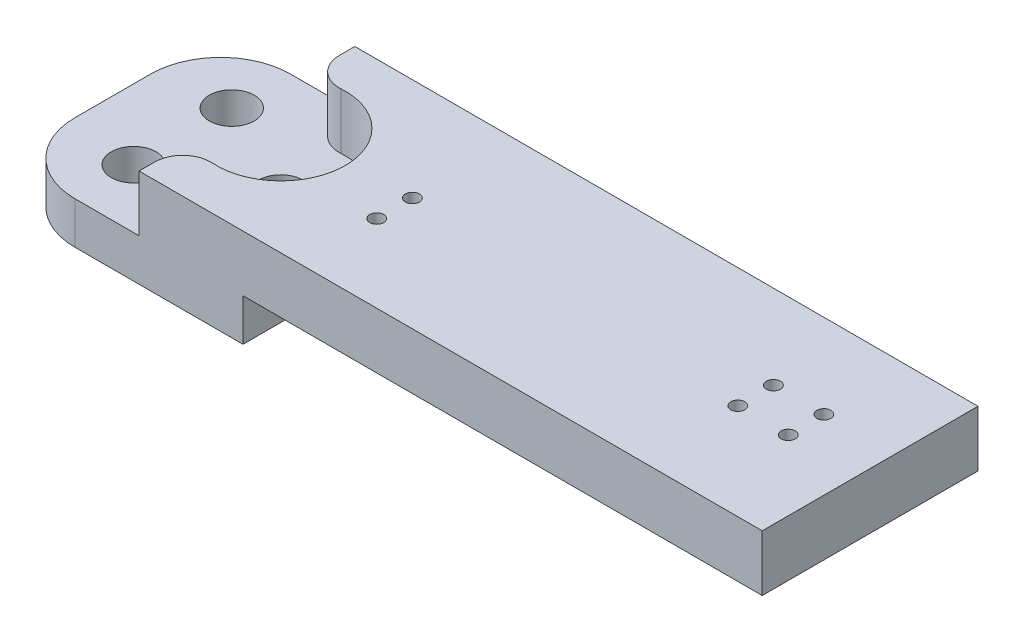
SolidWorks part; units mm, degrees
ref_plane "前视基准面" through (0, 0, 0) normal (0, 0, 1) x (1, 0, 0)
ref_plane "上视基准面" through (0, 0, 0) normal (0, 1, 0) x (1, 0, 0)
ref_plane "右视基准面" through (0, 0, 0) normal (1, 0, 0) x (0, 0, -1)
other "Configuration Table"
sketch "草图1" plane through (0, 0, 0) normal (0, 1, 0) x (1, 0, 0)
  line L0 (93.0116, 72.586) -> (93.0217, 72.586)
  line L1 (93.0116, 72.586) -> (93.0116, 72.6063)
  line L2 (93.0116, 72.586) -> (93.0217, 72.586)
  line L3 (93.0116, 72.586) -> (93.0116, 72.6063)
  line L4 (93.0116, 72.586) -> (93.0217, 72.586)
  line L5 (93.0116, 72.586) -> (93.0116, 72.6063)
  line L6 (103.9336, 94.432) -> (103.9437, 94.432)
  line L7 (103.9336, 94.432) -> (103.9336, 94.4523)
  line L8 (168.0366, 84.272) -> (168.0366, 84.2822)
  line L9 (168.0366, 84.272) -> (168.0163, 84.272)
  line L10 (158.1141, 95.514) -> (158.1039, 95.514)
  line L11 (158.1141, 95.514) -> (158.1141, 95.4938)
  line L12 (107.4956, 78.486) -> (107.4956, 78.4759)
  line L13 (107.4956, 78.486) -> (107.5158, 78.486)
  line L14 (161.3376, 94.432) -> (161.3477, 94.432)
  line L15 (161.3376, 94.432) -> (161.3376, 94.4523)
  line L16 (98.6366, 91.661) -> (98.6366, 91.6712)
  line L17 (98.6366, 91.661) -> (98.6163, 91.661)
  line L18 (100.7956, 90.686) -> (100.7956, 90.6962)
  line L19 (100.7956, 90.686) -> (100.7753, 90.686)
  line L20 (164.6396, 89.352) -> (164.6294, 89.352)
  line L21 (164.6396, 89.352) -> (164.6396, 89.3318)
  line L22 (94.7616, 80.161) -> (94.7514, 80.161)
  line L23 (94.7616, 80.161) -> (94.7616, 80.1408)
  line L24 (168.1956, 81.732) -> (168.1854, 81.732)
  line L25 (168.1956, 81.732) -> (168.1956, 81.7118)
  line L26 (178.2616, 97.586) -> (178.2514, 97.586)
  line L27 (178.2616, 97.586) -> (178.2616, 97.5658)
  line L28 (172.9366, 94.061) -> (172.9366, 94.0712)
  line L29 (172.9366, 94.061) -> (172.9163, 94.061)
  line L30 (113.8866, 87.236) -> (113.8764, 87.236)
  line L31 (113.8866, 87.236) -> (113.8866, 87.2158)
  line L32 (165.6556, 84.272) -> (165.6556, 84.2619)
  line L33 (165.6556, 84.272) -> (165.6758, 84.272)
  line L34 (115.6116, 92.886) -> (115.6116, 92.8759)
  line L35 (115.6116, 92.886) -> (115.6318, 92.886)
  line L36 (99.6366, 91.636) -> (99.6366, 91.6462)
  line L37 (99.6366, 91.636) -> (99.6163, 91.636)
  line L38 (106.2116, 94.486) -> (106.2217, 94.486)
  line L39 (106.2116, 94.486) -> (106.2116, 94.5063)
  line L40 (176.0696, 87.066) -> (176.0696, 87.0762)
  line L41 (176.0696, 87.066) -> (176.0493, 87.066)
  line L42 (175.5866, 82.236) -> (175.5967, 82.236)
  line L43 (175.5866, 82.236) -> (175.5866, 82.2563)
  line L44 (175.5616, 90.368) -> (175.5717, 90.368)
  line L45 (175.5616, 90.368) -> (175.5616, 90.3883)
  line L46 (95.0616, 85.036) -> (95.0514, 85.036)
  line L47 (95.0616, 85.036) -> (95.0616, 85.0158)
  line L48 (170.3616, 84.526) -> (170.3616, 84.5159)
  line L49 (170.3616, 84.526) -> (170.3818, 84.526)
  line L50 (156.2576, 97.48) -> (156.2576, 97.4699)
  line L51 (156.2576, 97.48) -> (156.2778, 97.48)
  line L52 (165.4016, 77.414) -> (165.4016, 77.4039)
  line L53 (165.4016, 77.414) -> (165.4218, 77.414)
  line L54 (166.1636, 90.368) -> (166.1737, 90.368)
  line L55 (166.1636, 90.368) -> (166.1636, 90.3883)
  line L56 (170.4816, 89.098) -> (170.4816, 89.1082)
  line L57 (170.4816, 89.098) -> (170.4613, 89.098)
  line L58 (114.7116, 89.836) -> (114.7116, 89.8462)
  line L59 (114.7116, 89.836) -> (114.6913, 89.836)
  line L60 (174.4366, 96.386) -> (174.4366, 96.3962)
  line L61 (174.4366, 96.386) -> (174.4163, 96.386)
  line L62 (186.9916, 88.59) -> (186.9916, 88.5799)
  line L63 (186.9916, 88.59) -> (187.0118, 88.59)
  line L64 (103.7141, 76.086) -> (103.7242, 76.086)
  line L65 (103.7141, 76.086) -> (103.7141, 76.1063)
  line L66 (184.9436, 88.0845) -> (184.9436, 88.0744)
  line L67 (184.9436, 88.0845) -> (184.9638, 88.0845)
  line L68 (122.8116, 84.011) -> (122.8217, 84.011)
  line L69 (122.8116, 84.011) -> (122.8116, 84.0313)
  line L70 (120.9516, 99.512) -> (120.9414, 99.512)
  line L71 (120.9516, 99.512) -> (120.9516, 99.4918)
  line L72 (173.1116, 80.97) -> (173.1116, 80.9802)
  line L73 (173.1116, 80.97) -> (173.0913, 80.97)
  line L74 (117.6116, 92.911) -> (117.6116, 92.9212)
  line L75 (117.6116, 92.911) -> (117.5913, 92.911)
  line L76 (112.3156, 92.908) -> (112.3257, 92.908)
  line L77 (112.3156, 92.908) -> (112.3156, 92.9283)
  line L78 (120.9516, 97.988) -> (120.9414, 97.988)
  line L79 (120.9516, 97.988) -> (120.9516, 97.9678)
  line L80 (163.1156, 87.32) -> (163.1156, 87.3099)
  line L81 (163.1156, 87.32) -> (163.1358, 87.32)
  line L82 (103.7141, 75.086) -> (103.7039, 75.086)
  line L83 (103.7141, 75.086) -> (103.7141, 75.0658)
  line L84 (116.6366, 92.886) -> (116.6366, 92.8962)
  line L85 (116.6366, 92.886) -> (116.6163, 92.886)
  line L86 (108.2516, 75.636) -> (108.2414, 75.636)
  line L87 (108.2516, 75.636) -> (108.2516, 75.6158)
  line L88 (185.9756, 88.082) -> (185.9756, 88.0922)
  line L89 (185.9756, 88.082) -> (185.9553, 88.082)
  line L90 (104.5616, 81.486) -> (104.5514, 81.486)
  line L91 (104.5616, 81.486) -> (104.5616, 81.4658)
  line L92 (101.8116, 90.686) -> (101.8116, 90.6962)
  line L93 (101.8116, 90.686) -> (101.7913, 90.686)
  line L94 (102.8616, 82.886) -> (102.8616, 82.8759)
  line L95 (102.8616, 82.886) -> (102.8818, 82.886)
  line L96 (106.2116, 95.486) -> (106.2217, 95.486)
  line L97 (106.2116, 95.486) -> (106.2116, 95.5063)
  line L98 (101.1396, 75.636) -> (101.1396, 75.6462)
  line L99 (101.1396, 75.636) -> (101.1193, 75.636)
  line L100 (97.0116, 90.486) -> (97.0014, 90.486)
  line L101 (97.0116, 90.486) -> (97.0116, 90.4658)
  line L102 (102.7866, 90.786) -> (102.7866, 90.7962)
  line L103 (102.7866, 90.786) -> (102.7663, 90.786)
  line L104 (167.7116, 87.911) -> (167.7116, 87.9009)
  line L105 (167.7116, 87.911) -> (167.7318, 87.911)
  line L106 (166.1636, 91.384) -> (166.1534, 91.384)
  line L107 (166.1636, 91.384) -> (166.1636, 91.3638)
  line L108 (97.0116, 89.486) -> (97.0014, 89.486)
  line L109 (97.0116, 89.486) -> (97.0116, 89.4658)
  line L110 (100.1236, 75.636) -> (100.1236, 75.6462)
  line L111 (100.1236, 75.636) -> (100.1033, 75.636)
  line L112 (172.0866, 80.62) -> (172.0866, 80.6302)
  line L113 (172.0866, 80.62) -> (172.0663, 80.62)
  line L114 (108.4991, 87.3235) -> (108.4991, 87.3337)
  line L115 (108.4991, 87.3235) -> (108.4788, 87.3235)
  line L116 (185.2136, 89.86) -> (185.2237, 89.86)
  line L117 (185.2136, 89.86) -> (185.2136, 89.8803)
  line L118 (173.2756, 88.844) -> (173.2756, 88.8339)
  line L119 (173.2756, 88.844) -> (173.2958, 88.844)
  line L120 (171.9366, 94.036) -> (171.9366, 94.0259)
  line L121 (171.9366, 94.036) -> (171.9568, 94.036)
  line L122 (170.2276, 93.924) -> (170.2276, 93.9139)
  line L123 (170.2276, 93.924) -> (170.2478, 93.924)
  line L124 (175.5866, 79.586) -> (175.5967, 79.586)
  line L125 (175.5866, 79.586) -> (175.5866, 79.6063)
  line L126 (180.5391, 83.002) -> (180.5492, 83.002)
  line L127 (180.5391, 83.002) -> (180.5391, 83.0223)
  line L128 (119.2116, 84.011) -> (119.2217, 84.011)
  line L129 (119.2116, 84.011) -> (119.2116, 84.0313)
  line L130 (107.7116, 74.186) -> (107.7217, 74.186)
  line L131 (107.7116, 74.186) -> (107.7116, 74.2063)
  line L132 (107.6116, 80.886) -> (107.6116, 80.8759)
  line L133 (107.6116, 80.886) -> (107.6318, 80.886)
  line L134 (103.7866, 91.561) -> (103.7866, 91.5712)
  line L135 (103.7866, 91.561) -> (103.7663, 91.561)
  line L136 (108.5866, 80.886) -> (108.5866, 80.8759)
  line L137 (108.5866, 80.886) -> (108.6068, 80.886)
  line L138 (165.5262, 99.6668) -> (182.5442, 99.6668)
  line L139 (182.5442, 99.6668) -> (182.5442, 96.8728)
  line L140 (96.8824, 77.3808) -> (96.6276, 77.6237)
  line L141 (96.6276, 77.6237) -> (96.3469, 77.836)
  line L142 (96.0438, 78.0149) -> (95.7224, 78.1582)
  line L143 (95.7224, 78.1582) -> (95.3867, 78.264)
  line L144 (164.7642, 100.4288) -> (165.5262, 99.6668)
  line L145 (164.5669, 88.1518) -> (164.4036, 88.0947)
  line L146 (164.4036, 88.0947) -> (164.2571, 88.0026)
  line L147 (164.2571, 88.0026) -> (164.1348, 87.8803)
  line L148 (164.1348, 87.8803) -> (164.0427, 87.7338)
  line L149 (164.1348, 86.917) -> (164.2571, 86.7947)
  line L150 (164.2571, 86.7947) -> (164.4036, 86.7026)
  line L151 (164.4036, 86.7026) -> (164.5669, 86.6455)
  line L152 (164.5669, 86.6455) -> (164.7388, 86.6261)
  line L153 (164.7388, 86.6261) -> (164.9107, 86.6455)
  line L154 (165.4919, 87.2267) -> (165.5113, 87.3986)
  line L155 (165.5113, 87.3986) -> (165.4919, 87.5705)
  line L156 (165.4919, 87.5705) -> (165.4348, 87.7338)
  line L157 (165.4348, 87.7338) -> (165.3427, 87.8803)
  line L158 (165.3427, 87.8803) -> (165.2204, 88.0026)
  line L159 (137.7132, 95.8568) -> (137.144, 95.8353)
  line L160 (151.1426, 85.7394) -> (151.3379, 85.9384)
  line L161 (151.8102, 87.2208) -> (151.7905, 87.499)
  line L162 (151.7905, 87.499) -> (151.7319, 87.7716)
  line L163 (151.7319, 87.7716) -> (151.6355, 88.0333)
  line L164 (151.6355, 88.0333) -> (151.5033, 88.2788)
  line L165 (151.5033, 88.2788) -> (151.3379, 88.5033)
  line L166 (139.9573, 95.5149) -> (139.4075, 95.6639)
  line L167 (139.4075, 95.6639) -> (138.8482, 95.7709)
  line L168 (138.8482, 95.7709) -> (138.2823, 95.8353)
  line L169 (138.2823, 95.8353) -> (137.7132, 95.8568)
  line L170 (118.0282, 100.4288) -> (164.7642, 100.4288)
  line L171 (182.5442, 96.8728) -> (182.6167, 96.5552)
  line L172 (118.0282, 98.6508) -> (118.0282, 100.4288)
  line L173 (182.6167, 96.5552) -> (182.7281, 96.249)
  line L174 (97.8352, 98.6508) -> (118.0282, 98.6508)
  line L175 (182.7281, 96.249) -> (182.8767, 95.9591)
  line L176 (97.8352, 94.5868) -> (97.8352, 98.6508)
  line L177 (182.8767, 95.9591) -> (183.0603, 95.6899)
  line L178 (97.8236, 94.2665) -> (97.8352, 94.5868)
  line L179 (183.0603, 95.6899) -> (183.2759, 95.4456)
  line L180 (97.7731, 93.95) -> (97.8236, 94.2665)
  line L181 (183.2759, 95.4456) -> (183.5202, 95.23)
  line L182 (97.6844, 93.642) -> (97.7731, 93.95)
  line L183 (183.5202, 95.23) -> (183.7894, 95.0464)
  line L184 (97.5587, 93.3471) -> (97.6844, 93.642)
  line L185 (183.7894, 95.0464) -> (184.0793, 94.8978)
  line L186 (97.398, 93.0697) -> (97.5587, 93.3471)
  line L187 (184.0793, 94.8978) -> (184.3855, 94.7864)
  line L188 (97.2046, 92.8141) -> (97.398, 93.0697)
  line L189 (184.3855, 94.7864) -> (184.7032, 94.7138)
  line L190 (96.9815, 92.5839) -> (97.2046, 92.8141)
  line L191 (184.7032, 94.7138) -> (188.8942, 94.7138)
  line L192 (96.732, 92.3827) -> (96.9815, 92.5839)
  line L193 (188.8942, 94.7138) -> (188.8942, 78.3308)
  line L194 (96.4599, 92.2134) -> (96.732, 92.3827)
  line L195 (188.8942, 78.3308) -> (177.4642, 78.3308)
  line L196 (96.169, 92.0786) -> (96.4599, 92.2134)
  line L197 (177.4642, 78.3308) -> (177.1354, 78.2515)
  line L198 (95.864, 91.9802) -> (96.169, 92.0786)
  line L199 (177.1354, 78.2515) -> (176.8186, 78.1328)
  line L200 (95.5492, 91.9198) -> (95.864, 91.9802)
  line L201 (176.8186, 78.1328) -> (176.5187, 77.9765)
  line L202 (93.0092, 91.9198) -> (95.5492, 91.9198)
  line L203 (176.5187, 77.9765) -> (176.2399, 77.7849)
  line L204 (93.0092, 88.1098) -> (93.0092, 91.9198)
  line L205 (176.2399, 77.7849) -> (175.9866, 77.5609)
  line L206 (95.5492, 88.1098) -> (93.0092, 88.1098)
  line L207 (175.9866, 77.5609) -> (175.7623, 77.3077)
  line L208 (95.7229, 88.0427) -> (95.5492, 88.1098)
  line L209 (175.7623, 77.3077) -> (175.5704, 77.0292)
  line L210 (95.878, 87.9395) -> (95.7229, 88.0427)
  line L211 (175.5704, 77.0292) -> (175.4138, 76.7294)
  line L212 (96.007, 87.8051) -> (95.878, 87.9395)
  line L213 (175.4138, 76.7294) -> (175.2949, 76.4128)
  line L214 (96.1038, 87.6459) -> (96.007, 87.8051)
  line L215 (175.2949, 76.4128) -> (175.2152, 76.084)
  line L216 (96.1638, 87.4695) -> (96.1038, 87.6459)
  line L217 (175.2152, 76.084) -> (175.1761, 75.7481)
  line L218 (96.1842, 87.2843) -> (96.1638, 87.4695)
  line L219 (175.1761, 75.7481) -> (175.1782, 75.4098)
  line L220 (96.1638, 87.0992) -> (96.1842, 87.2843)
  line L221 (175.1782, 75.4098) -> (175.1782, 75.0288)
  line L222 (96.1038, 86.9228) -> (96.1638, 87.0992)
  line L223 (175.1782, 75.0288) -> (161.4622, 75.0288)
  line L224 (96.007, 86.7636) -> (96.1038, 86.9228)
  line L225 (161.4622, 75.0288) -> (161.4622, 72.6158)
  line L226 (95.878, 86.6292) -> (96.007, 86.7636)
  line L227 (161.4622, 72.6158) -> (97.5812, 72.6158)
  line L228 (95.7229, 86.526) -> (95.878, 86.6292)
  line L229 (97.5812, 72.6158) -> (97.5812, 76.1718)
  line L230 (95.5492, 86.4588) -> (95.7229, 86.526)
  line L231 (97.5812, 76.1718) -> (97.4595, 76.5021)
  line L232 (93.0092, 86.4588) -> (95.5492, 86.4588)
  line L233 (97.4595, 76.5021) -> (97.301, 76.8164)
  line L234 (93.0092, 78.3308) -> (93.0092, 86.4588)
  line L235 (97.301, 76.8164) -> (97.1078, 77.1105)
  line L236 (95.0412, 78.3308) -> (93.0092, 78.3308)
  line L237 (97.1078, 77.1105) -> (96.8824, 77.3808)
  line L238 (95.3867, 78.264) -> (95.0412, 78.3308)
  line L239 (138.4395, 78.6481) -> (139.0038, 78.7263)
  line L240 (137.871, 78.6089) -> (138.4395, 78.6481)
  line L241 (137.3013, 78.6089) -> (137.871, 78.6089)
  line L242 (96.3469, 77.836) -> (96.0438, 78.0149)
  line L243 (164.7388, 88.1712) -> (164.5669, 88.1518)
  line L244 (164.9107, 88.1518) -> (164.7388, 88.1712)
  line L245 (165.0739, 88.0947) -> (164.9107, 88.1518)
  line L246 (165.2204, 88.0026) -> (165.0739, 88.0947)
  line L247 (134.0044, 79.4194) -> (134.5262, 79.1906)
  line L248 (133.4996, 79.6836) -> (134.0044, 79.4194)
  line L249 (133.0142, 79.9818) -> (133.4996, 79.6836)
  line L250 (123.9972, 85.6968) -> (133.0142, 79.9818)
  line L251 (123.8108, 85.8961) -> (123.9972, 85.6968)
  line L252 (165.4348, 87.0635) -> (165.4919, 87.2267)
  line L253 (165.3427, 86.917) -> (165.4348, 87.0635)
  line L254 (165.2204, 86.7947) -> (165.3427, 86.917)
  line L255 (165.0739, 86.7026) -> (165.2204, 86.7947)
  line L256 (164.9107, 86.6455) -> (165.0739, 86.7026)
  line L257 (123.3808, 87.4295) -> (123.3622, 87.1573)
  line L258 (123.4363, 87.6966) -> (123.3808, 87.4295)
  line L259 (123.5278, 87.9536) -> (123.4363, 87.6966)
  line L260 (123.6534, 88.1958) -> (123.5278, 87.9536)
  line L261 (123.8108, 88.4186) -> (123.6534, 88.1958)
  line L262 (164.0427, 87.0635) -> (164.1348, 86.917)
  line L263 (163.9856, 87.2267) -> (164.0427, 87.0635)
  line L264 (163.9662, 87.3986) -> (163.9856, 87.2267)
  line L265 (163.9856, 87.5705) -> (163.9662, 87.3986)
  line L266 (164.0427, 87.7338) -> (163.9856, 87.5705)
  line L267 (136.5782, 95.7709) -> (136.0188, 95.6639)
  line L268 (137.144, 95.8353) -> (136.5782, 95.7709)
  line L269 (186.4304, 92.0214) -> (186.4304, 93.139)
  line L270 (184.5508, 92.0214) -> (186.4304, 92.0214)
  line L271 (179.928, 93.139) -> (179.928, 92.0214)
  line L272 (181.8076, 93.139) -> (179.928, 93.139)
  line L273 (181.8076, 92.0214) -> (181.8076, 93.139)
  line L274 (140.4941, 95.3249) -> (139.9573, 95.5149)
  line L275 (141.0152, 95.0948) -> (140.4941, 95.3249)
  line L276 (150.9212, 88.8718) -> (141.0152, 95.0948)
  line L277 (151.1426, 88.7023) -> (150.9212, 88.8718)
  line L278 (151.3379, 88.5033) -> (151.1426, 88.7023)
  line L279 (176.7784, 94.9678) -> (176.7784, 93.0882)
  line L280 (177.896, 94.9678) -> (176.7784, 94.9678)
  line L281 (177.896, 93.0882) -> (177.896, 94.9678)
  line L282 (176.7784, 93.0882) -> (177.896, 93.0882)
  line L283 (171.038, 98.3206) -> (171.038, 97.203)
  line L284 (151.7905, 86.9427) -> (151.8102, 87.2208)
  line L285 (151.7319, 86.6701) -> (151.7905, 86.9427)
  line L286 (151.6355, 86.4084) -> (151.7319, 86.6701)
  line L287 (151.5033, 86.1629) -> (151.6355, 86.4084)
  line L288 (151.3379, 85.9384) -> (151.5033, 86.1629)
  line L289 (163.4688, 97.3554) -> (163.4688, 98.473)
  line L290 (150.9212, 85.5698) -> (151.1426, 85.7394)
  line L291 (142.1582, 79.9818) -> (150.9212, 85.5698)
  line L292 (141.6727, 79.6836) -> (142.1582, 79.9818)
  line L293 (141.1679, 79.4194) -> (141.6727, 79.6836)
  line L294 (140.6461, 79.1906) -> (141.1679, 79.4194)
  line L295 (140.1098, 78.9982) -> (140.6461, 79.1906)
  line L296 (139.5615, 78.8432) -> (140.1098, 78.9982)
  line L297 (139.0038, 78.7263) -> (139.5615, 78.8432)
  line L298 (136.7328, 78.6481) -> (137.3013, 78.6089)
  line L299 (136.1685, 78.7263) -> (136.7328, 78.6481)
  line L300 (135.6108, 78.8432) -> (136.1685, 78.7263)
  line L301 (135.0625, 78.9982) -> (135.6108, 78.8432)
  line L302 (134.5262, 79.1906) -> (135.0625, 78.9982)
  line L303 (134.4112, 95.0948) -> (123.9972, 88.6178)
  line L304 (134.9322, 95.3249) -> (134.4112, 95.0948)
  line L305 (179.928, 92.0214) -> (181.8076, 92.0214)
  line L306 (182.2648, 93.9518) -> (182.2648, 92.8342)
  line L307 (184.1444, 93.9518) -> (182.2648, 93.9518)
  line L308 (123.6534, 86.1189) -> (123.8108, 85.8961)
  line L309 (123.5278, 86.3611) -> (123.6534, 86.1189)
  line L310 (123.4363, 86.6181) -> (123.5278, 86.3611)
  line L311 (123.3808, 86.8852) -> (123.4363, 86.6181)
  line L312 (123.3622, 87.1573) -> (123.3808, 86.8852)
  line L313 (135.469, 95.5149) -> (134.9322, 95.3249)
  line L314 (136.0188, 95.6639) -> (135.469, 95.5149)
  line L315 (172.9176, 98.3206) -> (171.038, 98.3206)
  line L316 (172.9176, 97.203) -> (172.9176, 98.3206)
  line L317 (171.038, 97.203) -> (172.9176, 97.203)
  line L318 (123.9972, 88.6178) -> (123.8108, 88.4186)
  line L319 (161.5892, 98.473) -> (161.5892, 97.3554)
  line L320 (163.4688, 98.473) -> (161.5892, 98.473)
  line L321 (157.6268, 97.3554) -> (159.5064, 97.3554)
  line L322 (161.5892, 97.3554) -> (163.4688, 97.3554)
  line L323 (159.5064, 98.473) -> (157.6268, 98.473)
  line L324 (159.5064, 97.3554) -> (159.5064, 98.473)
  line L325 (184.1444, 92.8342) -> (184.1444, 93.9518)
  line L326 (186.4304, 93.139) -> (184.5508, 93.139)
  line L327 (184.5508, 93.139) -> (184.5508, 92.0214)
  line L328 (182.2648, 92.8342) -> (184.1444, 92.8342)
  line L329 (157.6268, 98.473) -> (157.6268, 97.3554)
  line L330 (119.5316, 81.791) -> (119.5316, 81.151)
  line L331 (118.8916, 81.151) -> (119.5316, 81.151)
  line L332 (118.8916, 81.791) -> (118.8916, 81.151)
  line L333 (118.8916, 81.791) -> (119.5316, 81.791)
  line L334 (119.5316, 84.331) -> (119.5316, 83.691)
  line L335 (118.8916, 84.331) -> (118.8916, 83.691)
  line L336 (118.8916, 84.331) -> (119.5316, 84.331)
  line L337 (118.8916, 83.691) -> (119.5316, 83.691)
  line L338 (122.4916, 81.791) -> (123.1316, 81.791)
  line L339 (122.4916, 81.151) -> (123.1316, 81.151)
  line L340 (122.4916, 81.791) -> (122.4916, 81.151)
  line L341 (123.1316, 81.791) -> (123.1316, 81.151)
  line L342 (123.1316, 84.331) -> (123.1316, 83.691)
  line L343 (122.4916, 83.691) -> (123.1316, 83.691)
  line L344 (122.4916, 84.331) -> (123.1316, 84.331)
  line L345 (122.4916, 84.331) -> (122.4916, 83.691)
  line L346 (94.4416, 79.841) -> (94.4416, 80.481)
  line L347 (95.0816, 80.481) -> (94.4416, 80.481)
  line L348 (95.0816, 79.841) -> (94.4416, 79.841)
  line L349 (95.0816, 79.841) -> (95.0816, 80.481)
  line L350 (94.4416, 82.381) -> (94.4416, 83.021)
  line L351 (95.0816, 83.021) -> (94.4416, 83.021)
  line L352 (95.0816, 82.381) -> (94.4416, 82.381)
  line L353 (95.0816, 82.381) -> (95.0816, 83.021)
  circle A0 centre (122.8116, 81.471) radius 0.5
  circle A1 centre (107.2241, 88.5985) radius 0.175
  circle A2 centre (109.7741, 86.0485) radius 0.175
  circle A3 centre (108.4991, 86.0485) radius 0.175
  circle A4 centre (107.2241, 86.0485) radius 0.175
  circle A5 centre (119.2116, 81.471) radius 0.5
  circle A6 centre (94.7616, 80.161) radius 0.5
  circle A7 centre (94.7616, 82.701) radius 0.5
  circle A8 centre (122.8116, 84.011) radius 0.5
  circle A9 centre (119.2116, 84.011) radius 0.5
  circle A10 centre (109.7741, 87.3235) radius 0.175
  circle A11 centre (108.4991, 87.3235) radius 0.175
  circle A12 centre (107.2241, 87.3235) radius 0.175
  circle A13 centre (109.7741, 88.5985) radius 0.175
  circle A14 centre (108.4991, 88.5985) radius 0.175
  point P204 (93.0116, 72.586)
  point P205 (93.0116, 72.586)
  point P206 (93.0116, 72.586)
  point P207 (103.9336, 94.432)
  point P208 (168.0366, 84.272)
  point P209 (158.1141, 95.514)
  point P210 (107.4956, 78.486)
  point P211 (161.3376, 94.432)
  point P212 (98.6366, 91.661)
  point P213 (100.7956, 90.686)
  point P214 (164.6396, 89.352)
  point P215 (94.7616, 80.161)
  point P216 (168.1956, 81.732)
  point P217 (178.2616, 97.586)
  point P218 (172.9366, 94.061)
  point P219 (113.8866, 87.236)
  point P220 (165.6556, 84.272)
  point P221 (115.6116, 92.886)
  point P222 (99.6366, 91.636)
  point P223 (106.2116, 94.486)
  point P224 (176.0696, 87.066)
  point P225 (175.5866, 82.236)
  point P226 (175.5616, 90.368)
  point P227 (95.0616, 85.036)
  point P228 (170.3616, 84.526)
  point P229 (156.2576, 97.48)
  point P230 (165.4016, 77.414)
  point P231 (166.1636, 90.368)
  point P232 (170.4816, 89.098)
  point P233 (114.7116, 89.836)
  point P234 (174.4366, 96.386)
  point P235 (186.9916, 88.59)
  point P236 (103.7141, 76.086)
  point P237 (184.9436, 88.0845)
  point P238 (122.8116, 84.011)
  point P239 (120.9516, 99.512)
  point P240 (173.1116, 80.97)
  point P241 (117.6116, 92.911)
  point P242 (112.3156, 92.908)
  point P243 (120.9516, 97.988)
  point P244 (163.1156, 87.32)
  point P245 (103.7141, 75.086)
  point P246 (116.6366, 92.886)
  point P247 (108.2516, 75.636)
  point P248 (185.9756, 88.082)
  point P249 (104.5616, 81.486)
  point P250 (101.8116, 90.686)
  point P251 (102.8616, 82.886)
  point P252 (106.2116, 95.486)
  point P253 (101.1396, 75.636)
  point P254 (97.0116, 90.486)
  point P255 (102.7866, 90.786)
  point P256 (167.7116, 87.911)
  point P257 (166.1636, 91.384)
  point P258 (97.0116, 89.486)
  point P259 (100.1236, 75.636)
  point P260 (172.0866, 80.62)
  point P261 (108.4991, 87.3235)
  point P262 (185.2136, 89.86)
  point P263 (173.2756, 88.844)
  point P264 (171.9366, 94.036)
  point P265 (170.2276, 93.924)
  point P266 (175.5866, 79.586)
  point P267 (180.5391, 83.002)
  point P268 (119.2116, 84.011)
  point P269 (107.7116, 74.186)
  point P270 (107.6116, 80.886)
  point P271 (103.7866, 91.561)
  point P272 (108.5866, 80.886)
sketch "草图2" plane through (0, 0, 0) normal (0, 1, 0) x (1, 0, 0)
  line L1 (125.8116, 76.6158) -> (90.7616, 76.6158)
  line L2 (125.8116, 76.6158) -> (125.8116, 88.011)
  line L3 (125.8116, 88.011) -> (90.7616, 88.011)
  line L4 (90.7616, 76.6158) -> (90.7616, 88.011)
  line L5 (125.8116, 76.6158) -> (90.7616, 88.011) construction
  line L6 (125.8116, 88.011) -> (90.7616, 76.6158) construction
  line L7 (161.4622, 72.6158) -> (97.5812, 72.6158) construction
  circle A0 centre (94.7616, 82.701) radius 0.6
  circle A1 centre (94.7616, 80.161) radius 0.6
  circle A2 centre (119.2116, 84.011) radius 0.6
  circle A3 centre (122.8116, 84.011) radius 0.6
  circle A4 centre (122.8116, 81.471) radius 0.6
  circle A5 centre (119.2116, 81.471) radius 0.6
  point P0 (94.7616, 82.701)
  point P1 (94.7616, 80.161)
  point P3 (119.2116, 84.011)
  point P5 (119.2116, 81.471)
  point P7 (122.8116, 84.011)
  point P9 (122.8116, 81.471)
  point P28 (108.2866, 82.3134)
  dimension "D1" = 1.2
  dimension "D2" = 3
  dimension "D3" = 4
  dimension "D4" = 4
  dimension "D5" = 4
extrude "凸台-拉伸1" add sketch "草图2" along normal blind 1.5
sketch "草图3" plane through (0, 1.5, 0) normal (0, 1, 0) x (1, 0, 0)
  line L12 (127.8116, 74.6158) -> (127.8116, 90.011)
  line L13 (127.8116, 90.011) -> (88.7616, 90.011)
  line L14 (88.7616, 90.011) -> (88.7616, 74.6158)
  line L15 (88.7616, 74.6158) -> (127.8116, 74.6158)
  line L16 (127.8116, 74.6158) -> (127.8116, 90.011)
  line L17 (127.8116, 90.011) -> (88.7616, 90.011)
  line L18 (88.7616, 90.011) -> (88.7616, 74.6158)
  line L19 (88.7616, 74.6158) -> (127.8116, 74.6158)
  circle A2 centre (94.7616, 82.701) radius 0.5
  circle A5 centre (94.7616, 80.161) radius 0.5
  circle A8 centre (119.2116, 84.011) radius 0.5
  circle A11 centre (122.8116, 84.011) radius 0.5
  circle A14 centre (122.8116, 81.471) radius 0.5
  circle A16 centre (119.2116, 81.471) radius 0.5
  dimension "D1" = 1
  dimension "D7" = 2
extrude "凸台-拉伸2" add sketch "草图3" along normal blind 4
sketch "草图4" plane through (0, 0, -90.011) normal (0, 0, -1) x (-1, 0, 0)
  line L0 (-127.8116, 1.5) -> (-88.7616, 1.5) construction
  line L1 (-88.7616, 5.5) -> (-73.7616, 5.5)
  line L2 (-88.7616, 5.5) -> (-88.7616, 1.5)
  line L3 (-88.7616, 1.5) -> (-73.7616, 1.5)
  line L4 (-73.7616, 5.5) -> (-73.7616, 1.5)
  line L5 (-88.7616, 5.5) -> (-73.7616, 1.5) construction
  line L6 (-88.7616, 1.5) -> (-73.7616, 5.5) construction
  point P4 (-81.2616, 3.5)
  dimension "D1" = 15
extrude "凸台-拉伸3" add sketch "草图4" against normal up to surface (15.3952 mm away) up to face at (108.2866, 3.5, -74.6158)
sketch "草图5" plane through (0, 1.5, 0) normal (0, -1, 0) x (1, 0, 0)
  line L0 (127.8116, -90.011) -> (73.7616, -90.011) construction
  line L1 (73.7616, -74.6158) -> (90.7616, -74.6158)
  line L2 (73.7616, -74.6158) -> (73.7616, -90.011)
  line L3 (73.7616, -90.011) -> (90.7616, -90.011)
  line L4 (90.7616, -74.6158) -> (90.7616, -90.011)
  line L5 (73.7616, -74.6158) -> (90.7616, -90.011) construction
  line L6 (73.7616, -90.011) -> (90.7616, -74.6158) construction
  line L7 (90.7616, -88.011) -> (90.7616, -76.6158) construction
  point P4 (82.2616, -82.3134)
extrude "凸台-拉伸4" add sketch "草图5" along normal blind 3
sketch "草图6" plane through (0, -1.5, 0) normal (0, -1, 0) x (1, 0, 0)
  line L0 (73.7616, -82.3134) -> (90.7616, -82.3134) construction
  line L1 (73.7616, -74.6158) -> (73.7616, -90.011) construction
  line L2 (90.7616, -88.011) -> (90.7616, -76.6158) construction
  line L3 (78.7616, -74.6158) -> (78.7616, -90.011) construction
  line L4 (90.7616, -74.6158) -> (73.7616, -74.6158) construction
  line L5 (73.7616, -90.011) -> (90.7616, -90.011) construction
  circle A0 centre (78.7616, -78.8134) radius 1.6
  circle A1 centre (85.7616, -82.3134) radius 1.6
  circle A2 centre (78.7616, -85.8134) radius 1.6
  dimension "D1" = 3.2
  dimension "D2" = 7
  dimension "D3" = 7
  dimension "D4" = 5
extrude "切除-拉伸1" cut sketch "草图6" against normal through all
sketch "草图7" plane through (0, 5.5, 0) normal (0, 1, 0) x (1, 0, 0)
  circle A0 centre (78.7616, 85.8134) radius 1.6 construction
  arc A1 (83.343, 86.2263) -> (75.7766, 82.3134) centre (78.7616, 85.8134) ccw
  circle A8 centre (85.7616, 82.3134) radius 4.6
  arc A9 (83.343, 78.4006) -> (83.343, 86.2263) centre (85.7616, 82.3134) ccw
  circle A11 centre (78.7616, 78.8134) radius 4.6
  arc A12 (75.7766, 82.3134) -> (83.343, 78.4006) centre (78.7616, 78.8134) ccw
  dimension "D1" = 3
  dimension "D2" = 3
  dimension "D3" = 3
extrude "切除-拉伸2" cut sketch "草图7" against normal offset from surface (4 mm away) 3 up to face at (78.7616, -1.5, -80.4134)
sketch "草图8" plane through (0, 5.5, 0) normal (0, 1, 0) x (1, 0, 0)
  line L0 (89.6957, 79.9296) -> (83.343, 78.4006)
  line L1 (83.343, 78.4006) -> (80.6431, 74.6158)
  line L2 (80.6431, 74.6158) -> (92.689, 74.6158)
  line L9 (127.8116, 90.011) -> (80.6431, 90.011) construction
  line L10 (80.6431, 74.6158) -> (127.8116, 74.6158) construction
  line L11 (92.689, 90.011) -> (80.6431, 90.011)
  line L15 (80.6431, 90.011) -> (83.343, 86.2263)
  line L16 (83.343, 86.2263) -> (89.6957, 84.6973)
  line L18 (76.88, 90.011) -> (73.7616, 90.011)
  line L19 (73.7616, 90.011) -> (73.7616, 74.6158)
  line L20 (73.7616, 74.6158) -> (76.88, 74.6158)
  line L21 (76.88, 90.011) -> (73.7616, 90.011)
  line L22 (73.7616, 90.011) -> (73.7616, 74.6158)
  line L23 (73.7616, 74.6158) -> (76.88, 74.6158)
  arc A8 (92.689, 90.011) -> (89.6957, 84.6973) centre (92.689, 86.511) ccw
  arc A9 (89.6957, 79.9296) -> (92.689, 74.6158) centre (92.689, 78.1158) ccw
  arc A10 (83.343, 78.4006) -> (83.343, 86.2263) centre (85.7616, 82.3134) ccw construction
  arc A11 (83.343, 78.4006) -> (83.343, 86.2263) centre (85.7616, 82.3134) ccw construction
  arc A16 (76.88, 90.011) -> (75.7766, 82.3134) centre (78.7616, 85.8134) ccw
  arc A17 (75.7766, 82.3134) -> (76.88, 74.6158) centre (78.7616, 78.8134) ccw
  arc A18 (76.88, 90.011) -> (75.7766, 82.3134) centre (78.7616, 85.8134) ccw
  arc A19 (75.7766, 82.3134) -> (76.88, 74.6158) centre (78.7616, 78.8134) ccw
  dimension "D1" = 7
  dimension "D2" = 0
extrude "切除-拉伸4" cut sketch "草图8" against normal up to surface (4 mm away) contours A18 A19 L23 L22 L21 up to face at (85.7616, 1.5, -83.9134)
fillet "圆角2" radius 5 2 edges at (73.7616, 0, -90.011) (73.7616, 0, -74.6158)
sketch "草图9" plane through (0, 5.5, 0) normal (0, 1, 0) x (1, 0, 0)
  line L0 (83.343, 86.2263) -> (83.343, 90.011)
  line L1 (127.8116, 90.011) -> (80.6431, 90.011) construction
  line L2 (83.343, 90.011) -> (80.6431, 90.011)
  line L3 (80.6431, 90.011) -> (83.343, 86.2263)
  line L4 (83.343, 78.4006) -> (83.343, 74.6158)
  line L5 (80.6431, 74.6158) -> (127.8116, 74.6158) construction
  line L6 (83.343, 74.6158) -> (80.6431, 74.6158)
  line L7 (80.6431, 74.6158) -> (83.343, 78.4006)
extrude "切除-拉伸5" cut sketch "草图9" against normal up to surface (4 mm away) up to face at (79.8741, 1.5, -82.3134)
fillet "圆角3" radius 2 2 edges at (83.343, 3.5, -78.4006) (83.343, 3.5, -86.2263)
sketch "草图10" plane through (0, -1.5, 0) normal (0, -1, 0) x (1, 0, 0)
  line L0 (85.7616, -82.3134) -> (85.7616, -73.1344) construction
  line L1 (81.7616, -82.3134) -> (88.5604, -82.3134) construction
  circle A0 centre (81.7616, -82.3134) radius 0.6
  circle A1 centre (85.7616, -77.3134) radius 0.6
  circle A2 centre (85.7616, -87.3134) radius 0.6
  dimension "D3" = 1.2
  dimension "D1" = 10
  dimension "D2" = 4
extrude "切除-拉伸6" cut sketch "草图10" against normal blind 2
